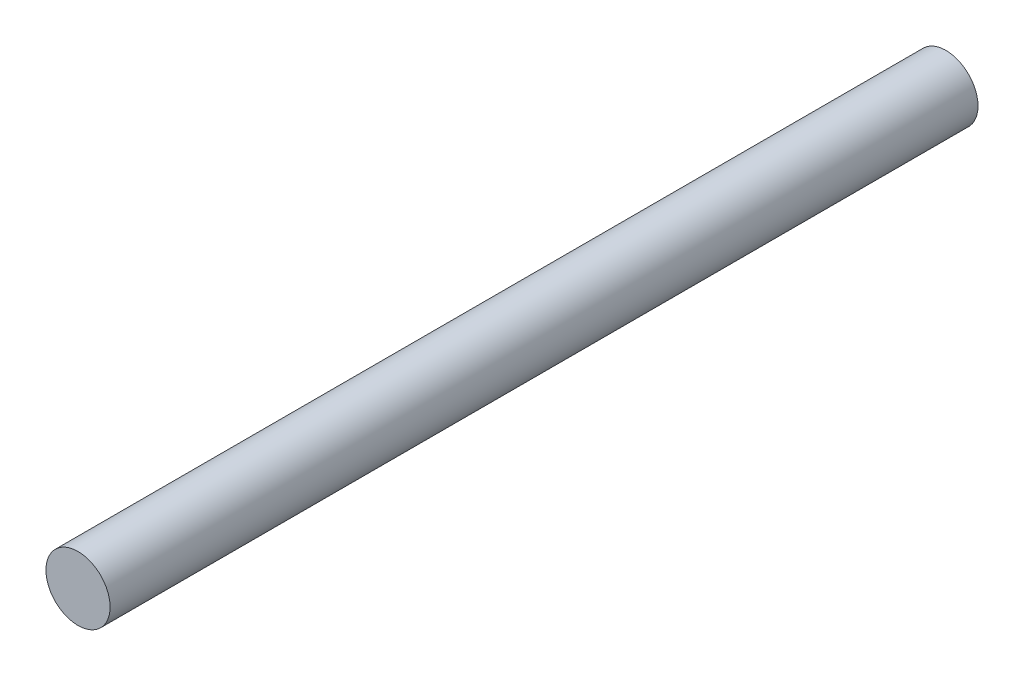
SolidWorks part; units mm, degrees
ref_plane "Front Plane" through (0, 0, 0) normal (0, 0, 1) x (1, 0, 0)
ref_plane "Top Plane" through (0, 0, 0) normal (0, 1, 0) x (1, 0, 0)
ref_plane "Right Plane" through (0, 0, 0) normal (1, 0, 0) x (0, 0, -1)
sketch "Sketch1" plane through (0, 0, 0) normal (0, 0, 1) x (1, 0, 0)
  circle A0 centre (0, 0) radius 4.7879
  dimension "D1" = 9.5758
extrude "Boss-Extrude1" add sketch "Sketch1" along normal blind 129.54
